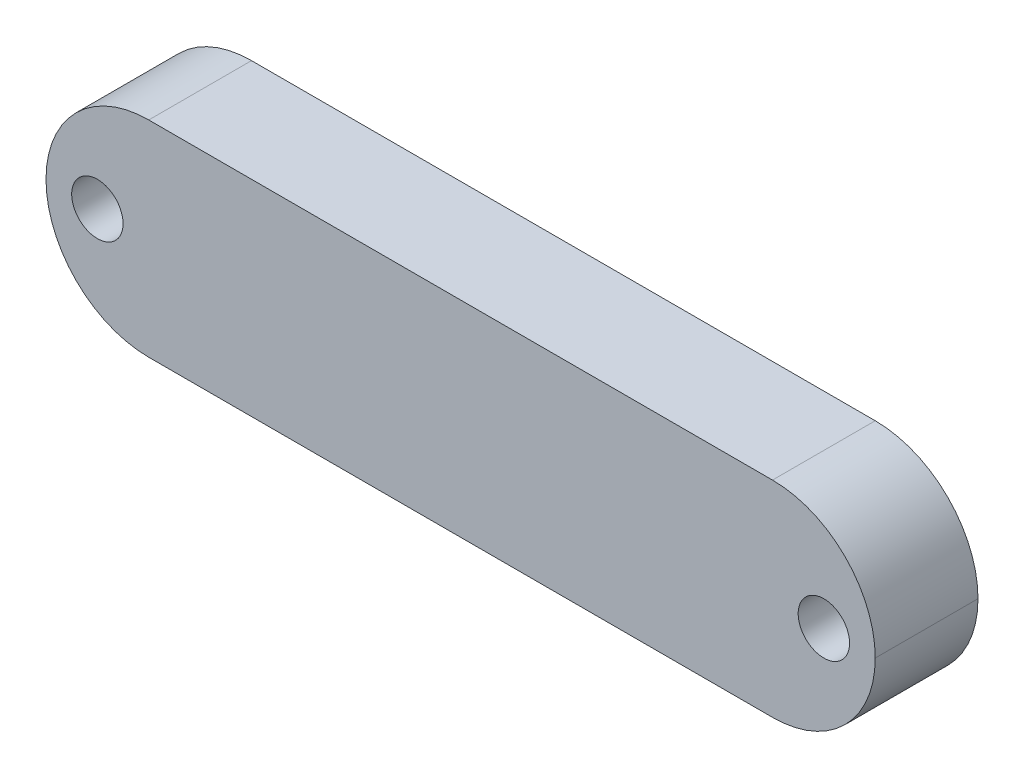
SolidWorks part; units mm, degrees
ref_plane "Front Plane" through (0, 0, 0) normal (0, 0, 1) x (1, 0, 0)
ref_plane "Top Plane" through (0, 0, 0) normal (0, 1, 0) x (1, 0, 0)
ref_plane "Right Plane" through (0, 0, 0) normal (1, 0, 0) x (0, 0, -1)
sketch "Sketch1" plane through (0, 0, 0) normal (0, 0, 1) x (1, 0, 0)
  line L1 (-40.35, 10) -> (40.35, 10)
  line L2 (-40.35, 10) -> (-40.35, -10)
  line L3 (-40.35, -10) -> (40.35, -10)
  line L4 (40.35, 10) -> (40.35, -10)
  line L5 (-40.35, 10) -> (40.35, -10) construction
  line L6 (-40.35, -10) -> (40.35, 10) construction
  circle A0 centre (-35.35, 0) radius 2.5
  circle A1 centre (35.35, 0) radius 2.5
  point P0 (0, 0)
  dimension "D4" = 5
  dimension "D5" = 5
  dimension "D6" = 5
  dimension "D1" = 80.7
  dimension "D2" = 20
  dimension "D3" = 5
extrude "Boss-Extrude1" add sketch "Sketch1" along normal blind 10
fillet "Fillet1" radius 10 4 edges at (40.35, -10, 5) (40.35, 10, 5) (-40.35, -10, 5) (-40.35, 10, 5)
